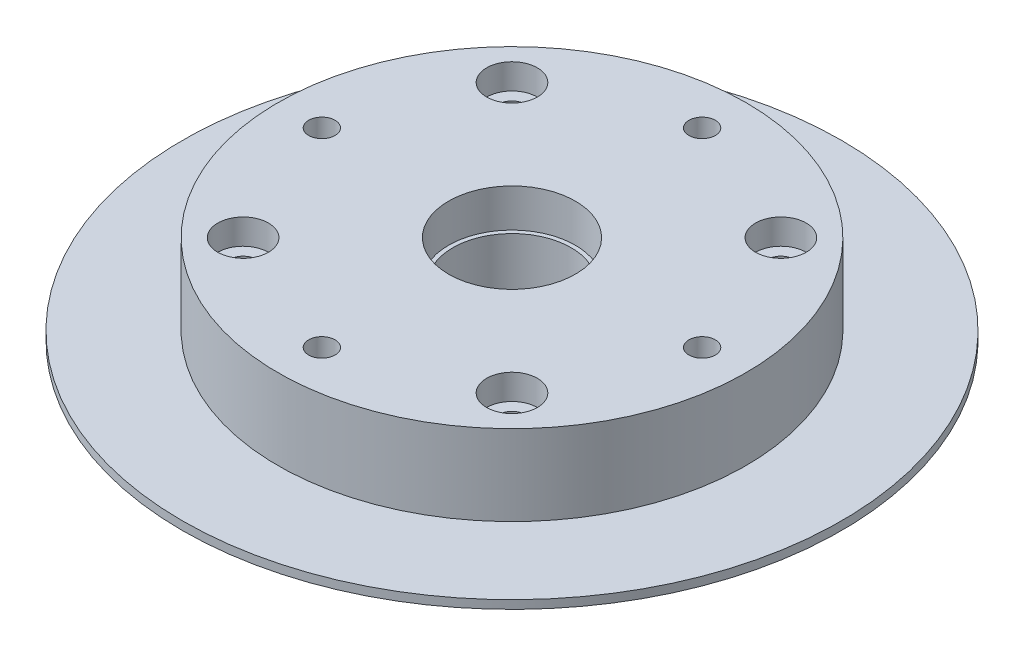
SolidWorks part; units mm, degrees
ref_plane "Front Plane" through (0, 0, 0) normal (0, 0, 1) x (1, 0, 0)
ref_plane "Top Plane" through (0, 0, 0) normal (0, 1, 0) x (1, 0, 0)
ref_plane "Right Plane" through (0, 0, 0) normal (1, 0, 0) x (0, 0, -1)
sketch "Sketch1" plane through (0, 0, 0) normal (0, 1, 0) x (1, 0, 0)
  line L0 (0, 0) -> (22.5, 0) construction
  circle A0 centre (0, 0) radius 39
  circle A1 centre (22.5, 0) radius 1.5635
  circle A2 centre (15.9099, -15.9099) radius 1.5635
  circle A3 centre (0, -22.5) radius 1.5635
  circle A4 centre (-15.9099, -15.9099) radius 1.5635
  circle A5 centre (-22.5, 0) radius 1.5635
  circle A6 centre (-15.9099, 15.9099) radius 1.5635
  circle A7 centre (0, 22.5) radius 1.5635
  circle A8 centre (15.9099, 15.9099) radius 1.5635
  circle A9 centre (0, 0) radius 7.5
  circle A10 centre (0, 0) radius 27.69
  circle A11 centre (0, 0) radius 7
  point P14 (0, 0)
  dimension "D2" = 78
  dimension "D3" = 15
  dimension "D5" = 3.127
  dimension "D6" = 55.38
  dimension "D7" = 14
  dimension "D4" = 22.5
  dimension "D1" = 8
extrude "Boss-Extrude1" add sketch "Sketch1" against normal blind 1 contours A0 A10 | A10 A2 A3 A4 A5 A6 A7 A8 A9 A1 region at (-37.8969, 0, 0) region at (-26.9068, 0, 0)
extrude "Boss-Extrude2" add sketch "Sketch1<3>" along normal blind 9.525 contours A10 A2 A3 A4 A5 A6 A7 A8 A9 A1 region at (-26.9068, 0, 0)
sketch "Sketch1<3>" plane through (0, 0, 0) normal (0, 1, 0) x (1, 0, 0) same geometry as "Sketch1"
sketch "Sketch2" plane through (0, 9.525, 0) normal (0, 1, 0) x (1, 0, 0)
  circle A0 centre (15.9099, 15.9099) radius 3
  circle A1 centre (15.9099, -15.9099) radius 3
  circle A2 centre (-15.9099, -15.9099) radius 3
  circle A3 centre (-15.9099, 15.9099) radius 3
  point P12 (0, 0)
  circle M4 centre (-15.9099, -15.9099) radius 1.5635
  circle M6 centre (-15.9099, 15.9099) radius 1.5635
  circle M8 centre (15.9099, 15.9099) radius 1.5635
  dimension "D1" = 6
  dimension "D2" = 4
extrude "Cut-Extrude1" cut sketch "Sketch2" against normal blind 3 contours A3 M6 | A0 M8 | A2 M4 | A1 region at (12.9948, 9.525, -15.9099) region at (-18.825, 9.525, 15.9099) region at (-18.825, 9.525, -15.9099)
extrude "Boss-Extrude3" add sketch "Sketch1<4>" against normal blind 1 contours A11 A9 region at (-7.2879, 0, 0)
sketch "Sketch1<4>" plane through (0, 0, 0) normal (0, 1, 0) x (1, 0, 0) same geometry as "Sketch1"
extrude "Boss-Extrude4" add sketch "Sketch1<5>" along normal blind 5 contours A11 A9 region at (-7.2879, 0, 0)
sketch "Sketch1<5>" plane through (0, 0, 0) normal (0, 1, 0) x (1, 0, 0) same geometry as "Sketch1"
sketch "Sketch3" plane through (0, -1, 0) normal (0, -1, 0) x (1, 0, 0)
  circle A0 centre (22.5, 0) radius 1.925
  circle A1 centre (0, -22.5) radius 1.925
  circle A2 centre (-22.5, 0) radius 1.925
  circle A3 centre (0, 22.5) radius 1.925
  point P12 (0, 0)
  dimension "D1" = 3.85
  dimension "D2" = 4
extrude "Cut-Extrude2" cut sketch "Sketch3" against normal blind 4
equation "\"D3@Sketch1\"=\"smallBearOD\"+\"smallBearOTight\""
equation "\"D1@Boss-Extrude2\"=\"sheetThickness\"*2"
equation "\"D1@Boss-Extrude4\"=\"thrustBearingThickness\""
equation "\"largeBearOD\"= 21mm"
equation "\"largeBearID\" = 15mm"
equation "\"largeBearOTight\"= 0.127mm'calibrate - hold onto gears"
equation "\"largeBearITight\"= 0mm'calibrate - hold onto eccentric nut"
equation "\"largeBearFlangeDiam\" = 22.5mm"
equation "\"largeBearFlangeWidth\" = 0.8mm"
equation "\"smallBearOD\"= 15mm"
equation "\"smallBearOTight\"= 0mm'calibrate - hold onto bottom of gearbox"
equation "\"smallBearOLoose\"= 0mm'calibrate - able to take off topHat"
equation "\"smallBearID\" = 10mm"
equation "\"smallBearITight\" = 0mm'hold onto "
equation "\"pinCircleDiam\"= 75mm"
equation "\"pinDiam\"= 6mm"
equation "\"sheetThickness\"= 0.1875in"
equation "\"ballBearDiam\"= 3.214mm"
equation "\"thrustBearingThickness\"= 5mm'measure this irl and change"
equation "\"thrustBearingID\"= 0mm'measure this irl and change"
equation "\"thrustBearingOD\"= 0mm'measure this irl and change"
equation "\"eccentricity\" = 1mm"
equation "\"D7@Sketch1\"=\"smallBearOD\"-1mm"
